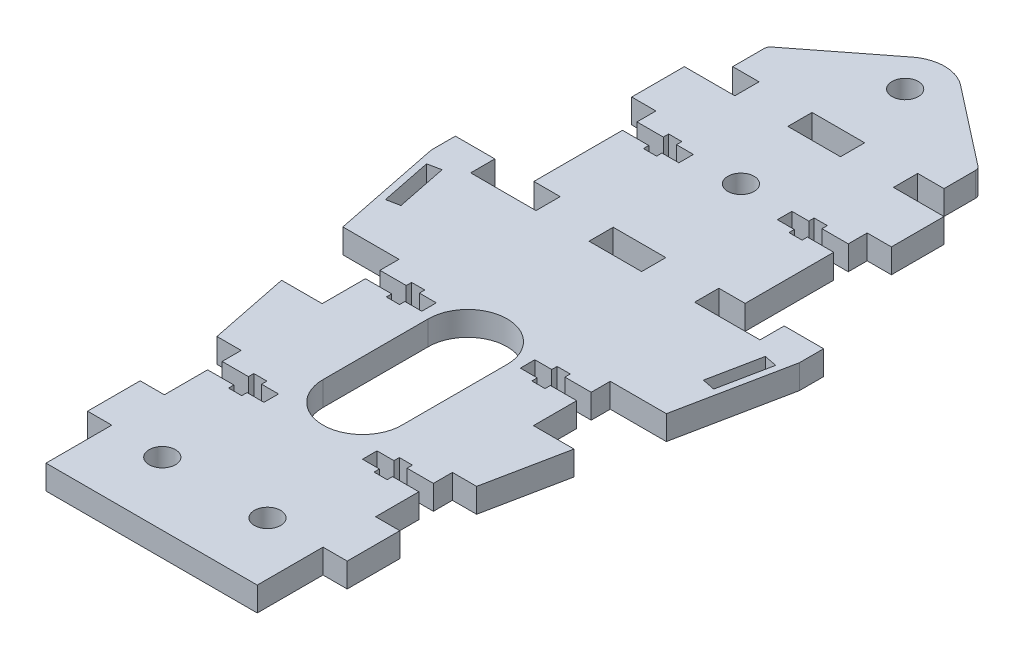
SolidWorks part; units mm, degrees
ref_plane "Front Plane" through (0, 0, 0) normal (0, 0, 1) x (1, 0, 0)
ref_plane "Top Plane" through (0, 0, 0) normal (0, 1, 0) x (1, 0, 0)
ref_plane "Right Plane" through (0, 0, 0) normal (1, 0, 0) x (0, 0, -1)
sketch "Sketch1" plane through (0, 0, 0) normal (0, 1, 0) x (1, 0, 0)
  line L0 (0, 96.7012) -> (0, 26.7242) construction
  line L1 (31.75, 26.7242) -> (25.5, 26.7242)
  line L2 (25.5, -85.217) -> (25.5, -69.342)
  line L3 (-25.5, -69.9464) -> (25.5, -69.9464) construction
  line L4 (0, 26.7242) -> (0, -69.9464) construction
  line L5 (25.5, -88.9) -> (-25.5, 88.9) construction
  line L6 (25.5, 88.9) -> (-25.5, -88.9) construction
  line L7 (-25.5, 77.6512) -> (25.5, 77.6512) construction
  line L8 (-25.5, -85.217) -> (-25.5, -69.342)
  line L9 (-25.5, 88.9) -> (-5.8561, 104.2134)
  line L10 (-25.5, 80.5722) -> (-25.5, 88.9)
  line L11 (5.8561, 104.2134) -> (25.5, 88.9)
  line L12 (-19.15, 74.7302) -> (-25.5, 74.7302)
  line L13 (-19.15, 74.7302) -> (-19.15, 80.5722)
  line L14 (-19.15, 80.5722) -> (-25.5, 80.5722)
  line L15 (19.15, 74.7302) -> (25.5, 74.7302)
  line L16 (-19.15, 74.7302) -> (-25.5, 80.5722) construction
  line L17 (-19.15, 80.5722) -> (-25.5, 74.7302) construction
  line L18 (6.35, 74.7302) -> (-6.35, 74.7302)
  line L19 (6.35, 74.7302) -> (6.35, 80.5722)
  line L20 (6.35, 80.5722) -> (-6.35, 80.5722)
  line L21 (-6.35, 74.7302) -> (-6.35, 80.5722)
  line L22 (6.35, 74.7302) -> (-6.35, 80.5722) construction
  line L23 (6.35, 80.5722) -> (-6.35, 74.7302) construction
  line L24 (19.15, 74.7302) -> (19.15, 80.5722)
  line L25 (19.15, 80.5722) -> (25.5, 80.5722)
  line L26 (25.5, 80.5722) -> (25.5, 88.9)
  line L27 (0, -69.9464) -> (0, -88.9) construction
  line L28 (0, -69.9464) -> (0, 26.7242) construction
  line L29 (0, -8.9111) -> (0, -34.3111) construction
  line L30 (9.525, -8.9111) -> (9.525, -34.3111)
  line L31 (-9.525, -8.9111) -> (-9.525, -34.3111)
  line L32 (-25.5, 53.6482) -> (25.5, 53.6482) construction
  line L33 (19.15, 32.5662) -> (25.5, 32.5662)
  line L34 (19.15, 32.5662) -> (19.15, 26.7242)
  line L35 (19.15, 26.7242) -> (25.5, 26.7242)
  line L36 (6.35, 32.5662) -> (6.35, 26.7242)
  line L37 (6.35, 32.5662) -> (-6.35, 32.5662)
  line L38 (6.35, 26.7242) -> (-6.35, 26.7242)
  line L39 (-6.35, 32.5662) -> (-6.35, 26.7242)
  line L40 (-19.15, 26.7242) -> (-25.5, 26.7242)
  line L41 (-19.15, 32.5662) -> (-19.15, 26.7242)
  line L42 (-19.15, 32.5662) -> (-25.5, 32.5662)
  line L43 (-25.5, 32.5662) -> (-25.5, 74.7302)
  line L44 (25.5, 32.5662) -> (25.5, 74.7302)
  line L45 (-44.45, 32.5662) -> (-34.925, 32.5662)
  line L46 (-31.75, 26.7242) -> (-25.5, 26.7242)
  line L47 (-44.45, 32.5662) -> (-44.45, 26.7242)
  line L48 (-25.5, -38.1) -> (-31.342, -38.1)
  line L49 (-34.925, 32.5662) -> (-34.925, 26.7242)
  line L50 (-44.45, 32.5662) -> (-31.75, 26.7242) construction
  line L51 (-44.45, 26.7242) -> (-31.75, 32.5662) construction
  line L52 (-31.342, -38.1) -> (-35.2968, -18.542)
  line L53 (-31.342, 0) -> (-39.0461, 0)
  line L54 (-31.342, -69.342) -> (-25.5, -69.342)
  line L55 (-31.342, -69.342) -> (-31.342, -56.642)
  line L56 (-31.342, -56.642) -> (-25.5, -56.642)
  line L57 (-25.5, -85.217) -> (25.5, -85.217)
  line L58 (-31.342, -69.342) -> (-25.5, -56.642) construction
  line L59 (-31.342, -56.642) -> (-25.5, -69.342) construction
  line L60 (-31.342, 0) -> (-25.5, 0)
  line L61 (-39.0461, 0) -> (-44.45, 26.7242)
  line L62 (-31.342, -18.542) -> (-25.5, -18.542)
  line L63 (-25.5, 0) -> (-25.5, -18.542)
  line L64 (-31.342, 0) -> (-25.5, -18.542) construction
  line L65 (-31.342, -18.542) -> (-25.5, 0) construction
  line L66 (-31.342, -18.542) -> (-35.2968, -18.542)
  line L67 (-25.5, -56.642) -> (-25.5, -38.1)
  line L68 (31.342, 0) -> (25.5, 0)
  line L69 (31.342, -18.542) -> (25.5, -18.542)
  line L70 (25.5, -38.1) -> (31.342, -38.1)
  line L71 (31.342, -69.342) -> (25.5, -69.342)
  line L72 (31.342, -56.642) -> (25.5, -56.642)
  line L73 (44.45, 32.5662) -> (44.45, 26.7242)
  line L74 (44.45, 32.5662) -> (34.925, 32.5662)
  line L75 (31.342, -18.542) -> (35.2968, -18.542)
  line L76 (39.0461, 0) -> (44.45, 26.7242)
  line L77 (31.342, -69.342) -> (31.342, -56.642)
  line L78 (31.342, 0) -> (39.0461, 0)
  line L79 (31.342, -38.1) -> (35.2968, -18.542)
  line L80 (34.925, 32.5662) -> (34.925, 26.7242)
  line L81 (34.925, 26.7242) -> (31.75, 26.7242)
  line L83 (25.5, -18.542) -> (25.5, 0)
  line L84 (25.5, -56.642) -> (25.5, -38.1)
  line L85 (-34.925, 26.7242) -> (-31.75, 26.7242)
  circle A0 centre (0, 96.7012) radius 3.175
  circle A1 centre (0, 57.0536) radius 3.175
  arc A4 (5.8561, 104.2134) -> (-5.8561, 104.2134) centre (0, 96.7012) ccw
  circle A5 centre (-12.7, -69.9464) radius 3.175
  circle A6 centre (12.7, -69.9464) radius 3.175
  arc A7 (9.525, -8.9111) -> (-9.525, -8.9111) centre (0, -8.9111) ccw
  arc A8 (-9.525, -34.3111) -> (9.525, -34.3111) centre (0, -34.3111) ccw
  point P0 (0, 0)
  point P14 (-38.1, 29.6452)
  point P17 (-6.35, 29.6452)
  point P21 (-22.325, 77.6512)
  point P28 (0, 77.6512)
  point P45 (0, -21.6111)
  point P66 (-28.421, -62.992)
  point P72 (-28.421, -9.271)
  point P97 (28.421, -9.271)
  point P98 (28.421, -62.992)
  point P99 (38.1, 29.6452)
  dimension "D3" = 6.35
  dimension "D4" = 6.35
  dimension "D5" = 39.6476
  dimension "D6" = 12.7
  dimension "D7" = 5.842
  dimension "D8" = 38.1
  dimension "D9" = 19.05
  dimension "D10" = 19.05
  dimension "D15" = 6.35
  dimension "D17" = 9.525
  dimension "D1" = 51
  dimension "D2" = 177.8
  dimension "D11" = 5.842
  dimension "D12" = 6.35
  dimension "D13" = 12.7
  dimension "D14" = 50.8
  dimension "D16" = 12.7
  dimension "D18" = 21.082
  dimension "D19" = 5.842
  dimension "D20" = 5.842
  dimension "D21" = 12.7
  dimension "D22" = 18.542
  dimension "D23" = 5.842
  dimension "D24" = 18.542
  dimension "D25" = 38.1
  dimension "D26" = 15.875
  dimension "D27" = 9.525
  dimension "D28" = 127
extrude "Boss-Extrude1" add sketch "Sketch1" along normal blind 5.842
sketch "Sketch2" plane through (0, 5.842, 0) normal (0, 1, 0) x (1, 0, 0)
  line L0 (0, 26.7242) -> (0, -85.217) construction
  line L1 (-6.35, 26.7242) -> (6.35, 26.7242) construction
  line L2 (-25.5, -85.217) -> (25.5, -85.217) construction
  line L3 (-25.5, -6.35) -> (25.5, -6.35) construction
  line L4 (-25.5, 0) -> (-25.5, -18.542) construction
  line L5 (25.5, -18.542) -> (25.5, 0) construction
  line L6 (-25.5, -44.45) -> (25.5, -44.45) construction
  line L7 (-25.5, -38.1) -> (-25.5, -56.642) construction
  line L8 (25.5, -56.642) -> (25.5, -38.1) construction
  line L9 (-39.0461, 0) -> (-25.5, 0) construction
  line L10 (-31.342, -38.1) -> (-25.5, -38.1) construction
  line L11 (-15.975, -42.6974) -> (-15.975, -41.402)
  line L12 (-19.15, -46.2026) -> (-25.5, -46.2026)
  line L13 (-1.3648, -6.35) -> (-1.3648, -44.45) construction
  line L14 (-19.15, -42.6974) -> (-25.5, -42.6974)
  line L15 (-25.5, -46.2026) -> (-25.5, -42.6974)
  line L16 (-19.15, -46.2026) -> (-25.5, -42.6974) construction
  line L17 (-19.15, -42.6974) -> (-25.5, -46.2026) construction
  line L18 (-15.975, -47.498) -> (-19.15, -47.498)
  line L19 (-15.975, -47.498) -> (-15.975, -46.2026)
  line L20 (-15.975, -41.402) -> (-19.15, -41.402)
  line L21 (-19.15, -47.498) -> (-19.15, -46.2026)
  line L22 (-15.975, -47.498) -> (-19.15, -41.402) construction
  line L23 (-15.975, -41.402) -> (-19.15, -47.498) construction
  line L24 (-11.892, -46.2026) -> (-15.975, -46.2026)
  line L25 (-11.892, -46.2026) -> (-11.892, -42.6974)
  line L26 (-11.892, -42.6974) -> (-15.975, -42.6974)
  line L27 (-19.15, -42.6974) -> (-19.15, -41.402)
  line L28 (-11.892, -46.2026) -> (-15.975, -42.6974) construction
  line L29 (-11.892, -42.6974) -> (-15.975, -46.2026) construction
  line L30 (-1.3648, -25.4) -> (0, -25.4) construction
  line L31 (-11.892, -8.1026) -> (-15.975, -4.5974) construction
  line L32 (-11.892, -4.5974) -> (-15.975, -8.1026) construction
  line L33 (-15.975, -9.398) -> (-19.15, -3.302) construction
  line L34 (-15.975, -3.302) -> (-19.15, -9.398) construction
  line L35 (-19.15, -8.1026) -> (-25.5, -4.5974) construction
  line L36 (-19.15, -4.5974) -> (-25.5, -8.1026) construction
  line L37 (-19.15, -8.1026) -> (-19.15, -9.398)
  line L38 (-11.892, -8.1026) -> (-15.975, -8.1026)
  line L39 (-11.892, -4.5974) -> (-11.892, -8.1026)
  line L40 (-11.892, -4.5974) -> (-15.975, -4.5974)
  line L41 (-19.15, -3.302) -> (-19.15, -4.5974)
  line L42 (-15.975, -9.398) -> (-19.15, -9.398)
  line L43 (-15.975, -3.302) -> (-15.975, -4.5974)
  line L44 (-15.975, -3.302) -> (-19.15, -3.302)
  line L45 (-25.5, -4.5974) -> (-25.5, -8.1026)
  line L46 (-19.15, -8.1026) -> (-25.5, -8.1026)
  line L47 (-19.15, -4.5974) -> (-25.5, -4.5974)
  line L48 (-15.975, -8.1026) -> (-15.975, -9.398)
  line L49 (19.15, -4.5974) -> (25.5, -8.1026) construction
  line L50 (19.15, -8.1026) -> (25.5, -4.5974) construction
  line L51 (15.975, -3.302) -> (19.15, -9.398) construction
  line L52 (15.975, -9.398) -> (19.15, -3.302) construction
  line L53 (11.892, -4.5974) -> (15.975, -8.1026) construction
  line L54 (11.892, -8.1026) -> (15.975, -4.5974) construction
  line L55 (11.892, -42.6974) -> (15.975, -46.2026) construction
  line L56 (11.892, -46.2026) -> (15.975, -42.6974) construction
  line L57 (15.975, -41.402) -> (19.15, -47.498) construction
  line L58 (15.975, -47.498) -> (19.15, -41.402) construction
  line L59 (19.15, -42.6974) -> (25.5, -46.2026) construction
  line L60 (19.15, -46.2026) -> (25.5, -42.6974) construction
  line L61 (15.975, -8.1026) -> (15.975, -9.398)
  line L62 (19.15, -4.5974) -> (25.5, -4.5974)
  line L63 (19.15, -8.1026) -> (25.5, -8.1026)
  line L64 (25.5, -4.5974) -> (25.5, -8.1026)
  line L65 (15.975, -3.302) -> (19.15, -3.302)
  line L66 (15.975, -3.302) -> (15.975, -4.5974)
  line L67 (15.975, -9.398) -> (19.15, -9.398)
  line L68 (19.15, -3.302) -> (19.15, -4.5974)
  line L69 (11.892, -4.5974) -> (15.975, -4.5974)
  line L70 (11.892, -4.5974) -> (11.892, -8.1026)
  line L71 (11.892, -8.1026) -> (15.975, -8.1026)
  line L72 (19.15, -8.1026) -> (19.15, -9.398)
  line L73 (19.15, -42.6974) -> (19.15, -41.402)
  line L74 (11.892, -42.6974) -> (15.975, -42.6974)
  line L75 (11.892, -46.2026) -> (11.892, -42.6974)
  line L76 (11.892, -46.2026) -> (15.975, -46.2026)
  line L77 (19.15, -47.498) -> (19.15, -46.2026)
  line L78 (15.975, -41.402) -> (19.15, -41.402)
  line L79 (15.975, -47.498) -> (15.975, -46.2026)
  line L80 (15.975, -47.498) -> (19.15, -47.498)
  line L81 (25.5, -46.2026) -> (25.5, -42.6974)
  line L82 (19.15, -42.6974) -> (25.5, -42.6974)
  line L83 (19.15, -46.2026) -> (25.5, -46.2026)
  line L84 (15.975, -42.6974) -> (15.975, -41.402)
  point P22 (-22.325, -44.45)
  point P27 (-17.5625, -44.45)
  point P32 (-13.9335, -44.45)
  point P53 (-13.9335, -6.35)
  point P54 (-17.5625, -6.35)
  point P55 (-22.325, -6.35)
  point P80 (22.325, -6.35)
  point P81 (17.5625, -6.35)
  point P82 (13.9335, -6.35)
  point P83 (13.9335, -44.45)
  point P84 (17.5625, -44.45)
  point P85 (22.325, -44.45)
  dimension "D1" = 6.35
  dimension "D2" = 6.35
  dimension "D3" = 3.5052
  dimension "D4" = 6.35
  dimension "D5" = 6.096
  dimension "D6" = 3.175
  dimension "D7" = 4.083
extrude "Cut-Extrude1" cut sketch "Sketch2" against normal through all
fillet "Fillet1" radius 1.5875 2 edges at (25.5, 2.921, -88.9) (-25.5, 2.921, -88.9)
sketch "Sketch3" plane through (0, 5.842, 0) normal (0, 1, 0) x (1, 0, 0)
  line L0 (-44.45, 26.7242) -> (44.45, 26.7242) construction
  line L2 (-41.2107, 26.7242) -> (-28.1027, -38.1) construction
  line L3 (-35.2968, -18.542) -> (-31.342, -38.1) construction
  line L4 (0, 26.7242) -> (0, -38.1) construction
  line L5 (-42.1375, 23.2976) -> (-39.6204, 10.8495)
  line L6 (-42.1375, 23.2976) -> (-39.0255, 23.9269)
  line L7 (-39.6204, 10.8495) -> (-36.5084, 11.4788)
  line L8 (-39.0255, 23.9269) -> (-36.5084, 11.4788)
  line L9 (-42.1375, 23.2976) -> (-36.5084, 11.4788) construction
  line L10 (-39.6204, 10.8495) -> (-39.0255, 23.9269) construction
  line L11 (-32.313, -5.214) -> (-37.0004, -6.1618) construction
  line L20 (32.313, -5.214) -> (37.0004, -6.1618) construction
  line L21 (39.6204, 10.8495) -> (39.0255, 23.9269) construction
  line L22 (42.1375, 23.2976) -> (36.5084, 11.4788) construction
  line L23 (41.2107, 26.7242) -> (28.1027, -38.1) construction
  line L28 (39.0255, 23.9269) -> (36.5084, 11.4788)
  line L29 (39.6204, 10.8495) -> (36.5084, 11.4788)
  line L30 (42.1375, 23.2976) -> (39.0255, 23.9269)
  line L31 (42.1375, 23.2976) -> (39.6204, 10.8495)
  point P15 (-39.3229, 17.3882)
  point P22 (-34.6567, -5.6879)
  point P40 (34.6567, -5.6879)
  point P41 (39.3229, 17.3882)
  dimension "D1" = 3.175
  dimension "D2" = 3.175
  dimension "D3" = 12.7
  dimension "D4" = 9.525
extrude "Cut-Extrude2" cut sketch "Sketch3" against normal through all
sketch "Sketch4" plane through (0, 5.842, 0) normal (0, 1, 0) x (1, 0, 0)
  line L0 (0, 74.7302) -> (0, 32.5662) construction
  line L1 (25.5, 74.7302) -> (31.342, 74.7302)
  line L2 (25.5, 74.7302) -> (25.5, 62.0302)
  line L3 (25.5, 62.0302) -> (31.342, 62.0302)
  line L4 (31.342, 74.7302) -> (31.342, 62.0302)
  line L5 (-6.35, 74.7302) -> (6.35, 74.7302) construction
  line L6 (6.35, 32.5662) -> (-6.35, 32.5662) construction
  line L7 (-31.342, 74.7302) -> (-31.342, 62.0302)
  line L8 (-25.5, 62.0302) -> (-31.342, 62.0302)
  line L9 (-25.5, 74.7302) -> (-25.5, 62.0302)
  line L10 (-25.5, 74.7302) -> (-31.342, 74.7302)
  dimension "D1" = 12.7
  dimension "D2" = 5.842
extrude "Boss-Extrude2" add sketch "Sketch4" against normal up to surface (5.842 mm away) up to face at (39.3229, 0, -17.3882)
sketch "Sketch5" plane through (0, 0, 0) normal (0, -1, 0) x (-1, 0, 0)
  line L0 (25.5, 55.709) -> (-25.5, 55.709) construction
  line L1 (25.5, 62.0302) -> (25.5, 32.5662) construction
  line L2 (-25.5, 32.5662) -> (-25.5, 62.0302) construction
  line L3 (15.975, 57.4616) -> (15.975, 58.757)
  line L4 (19.15, 57.4616) -> (25.5, 57.4616)
  line L5 (19.15, 57.4616) -> (19.15, 58.757)
  line L6 (19.15, 53.9564) -> (25.5, 53.9564)
  line L7 (25.5, 57.4616) -> (25.5, 53.9564)
  line L8 (19.15, 57.4616) -> (25.5, 53.9564) construction
  line L9 (19.15, 53.9564) -> (25.5, 57.4616) construction
  line L10 (15.975, 52.661) -> (19.15, 52.661)
  line L11 (15.975, 52.661) -> (15.975, 53.9564)
  line L12 (15.975, 58.757) -> (19.15, 58.757)
  line L13 (19.15, 52.661) -> (19.15, 53.9564)
  line L14 (15.975, 52.661) -> (19.15, 58.757) construction
  line L15 (15.975, 58.757) -> (19.15, 52.661) construction
  line L16 (11.892, 53.9564) -> (15.975, 53.9564)
  line L17 (11.892, 53.9564) -> (11.892, 57.4616)
  line L18 (11.892, 57.4616) -> (15.975, 57.4616)
  line L19 (19.15, 74.7302) -> (31.342, 74.7302) construction
  line L20 (11.892, 53.9564) -> (15.975, 57.4616) construction
  line L21 (11.892, 57.4616) -> (15.975, 53.9564) construction
  line L22 (0, 74.7302) -> (0, 32.5662) construction
  line L23 (6.35, 74.7302) -> (-6.35, 74.7302) construction
  line L24 (-6.35, 32.5662) -> (6.35, 32.5662) construction
  line L25 (-11.892, 57.4616) -> (-15.975, 53.9564) construction
  line L26 (-11.892, 53.9564) -> (-15.975, 57.4616) construction
  line L27 (-15.975, 58.757) -> (-19.15, 52.661) construction
  line L28 (-15.975, 52.661) -> (-19.15, 58.757) construction
  line L29 (-19.15, 53.9564) -> (-25.5, 57.4616) construction
  line L30 (-19.15, 57.4616) -> (-25.5, 53.9564) construction
  line L31 (-11.892, 57.4616) -> (-15.975, 57.4616)
  line L32 (-11.892, 53.9564) -> (-11.892, 57.4616)
  line L33 (-11.892, 53.9564) -> (-15.975, 53.9564)
  line L34 (-19.15, 52.661) -> (-19.15, 53.9564)
  line L35 (-15.975, 58.757) -> (-19.15, 58.757)
  line L36 (-15.975, 52.661) -> (-15.975, 53.9564)
  line L37 (-15.975, 52.661) -> (-19.15, 52.661)
  line L38 (-25.5, 57.4616) -> (-25.5, 53.9564)
  line L39 (-19.15, 53.9564) -> (-25.5, 53.9564)
  line L40 (-19.15, 57.4616) -> (-19.15, 58.757)
  line L41 (-19.15, 57.4616) -> (-25.5, 57.4616)
  line L42 (-15.975, 57.4616) -> (-15.975, 58.757)
  point P6 (22.325, 55.709)
  point P11 (17.5625, 55.709)
  point P16 (13.9335, 55.709)
  point P41 (-13.9335, 55.709)
  point P42 (-17.5625, 55.709)
  point P43 (-22.325, 55.709)
  dimension "D1" = 3.5052
  dimension "D2" = 6.35
  dimension "D3" = 3.175
  dimension "D4" = 6.096
  dimension "D5" = 4.083
  dimension "D6" = 19.0213
extrude "Cut-Extrude3" cut sketch "Sketch5" against normal through all
